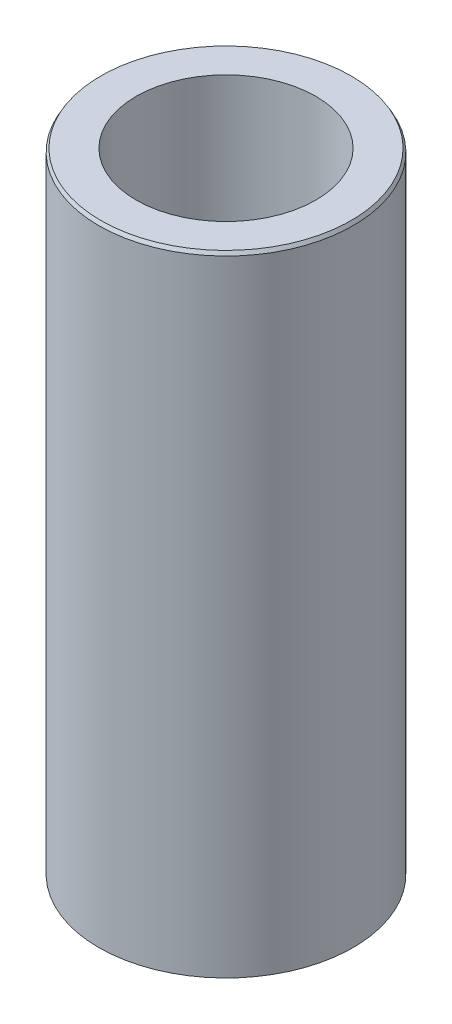
SolidWorks part; units mm, degrees
ref_plane "Front Plane" through (0, 0, 0) normal (0, 0, 1) x (1, 0, 0)
ref_plane "Top Plane" through (0, 0, 0) normal (0, 1, 0) x (1, 0, 0)
ref_plane "Right Plane" through (0, 0, 0) normal (1, 0, 0) x (0, 0, -1)
sketch "Sketch1" plane through (0, 0, 0) normal (0, 1, 0) x (1, 0, 0)
  circle A0 centre (0, 0) radius 50
  dimension "SHAFT_OD" = 100
extrude "Boss-Extrude1" add sketch "Sketch1" along normal blind 247.9053
sketch "Sketch2" plane through (0, 0, 0) normal (0, 1, 0) x (1, 0, 0)
  circle A0 centre (0, 0) radius 35.3265
  dimension "BORE_D" = 70.653
extrude "Cut-Extrude1" cut sketch "Sketch2" along normal through all
chamfer "Chamfer1" distance 1.3638 angle 30 2 edges at (0, 247.9053, 50) (0, 0, 50) first distance on face at (0, 247.9053, 50) first distance on face at (0, 0, 35.3265)
